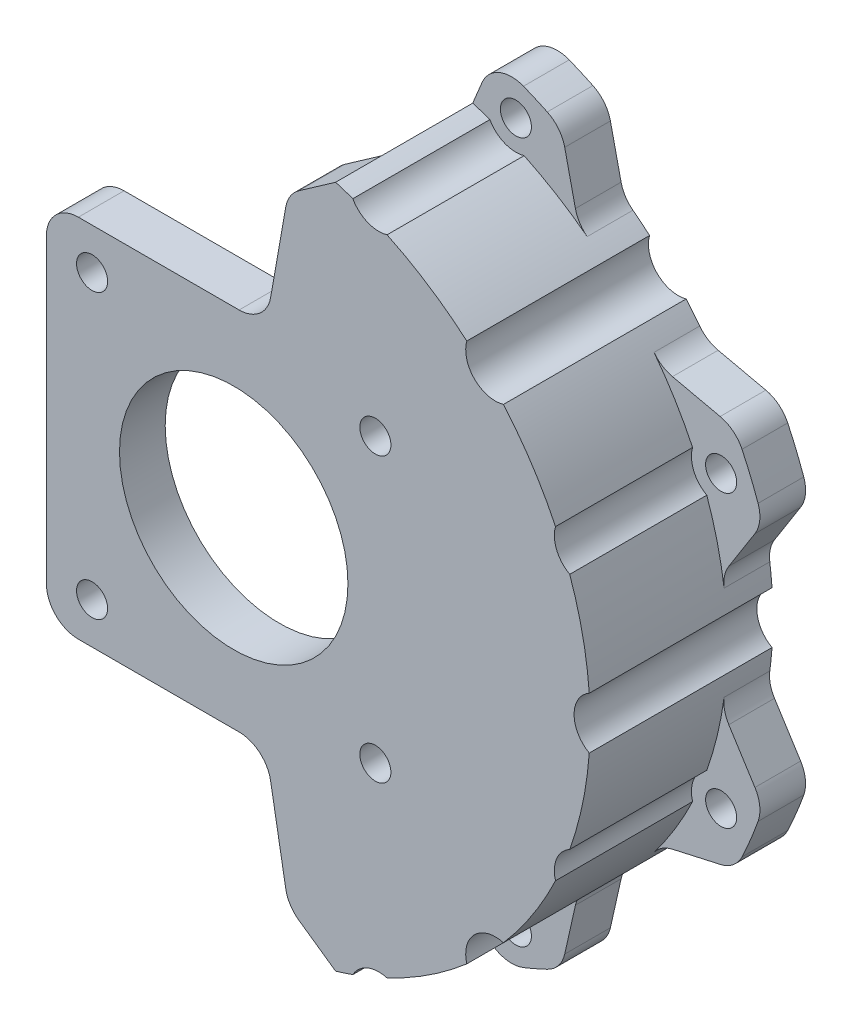
SolidWorks part; units mm, degrees
ref_plane "Alzado" through (0, 0, 0) normal (0, 0, 1) x (1, 0, 0)
ref_plane "Planta" through (0, 0, 0) normal (0, 1, 0) x (1, 0, 0)
ref_plane "Vista lateral" through (0, 0, 0) normal (1, 0, 0) x (0, 0, -1)
sketch "Croquis1" plane through (0, 0, 0) normal (0, 0, 1) x (1, 0, 0)
  line L0 (0, 0) -> (40.5, 0) construction
  line L1 (0, 0) -> (15.8814, 38.341) construction
  line L2 (13.4513, 42.9268) -> (10.7725, 36.4596)
  line L3 (0, 0) -> (38.341, 15.8814) construction
  line L4 (0, 0) -> (38.341, -15.8814) construction
  line L5 (0, 0) -> (15.8814, -38.341) construction
  line L7 (20.8423, 39.8653) -> (18.1635, 33.3982)
  line L8 (10.7725, 36.4596) -> (8.6471, 31.3285)
  line L9 (42.9268, 13.4513) -> (36.4596, 10.7725)
  line L10 (39.8653, 20.8423) -> (33.3982, 18.1635)
  line L11 (8.6471, -31.3285) -> (13.4513, -42.9268)
  line L12 (39.8653, -20.8423) -> (33.3982, -18.1635)
  line L13 (42.9268, -13.4513) -> (36.4596, -10.7725)
  line L16 (20.8423, -39.8653) -> (18.1635, -33.3982)
  line L18 (33.3982, 18.1635) -> (28.2671, 16.0382) [skipped]
  line L19 (36.4596, -10.7725) -> (31.3285, -8.6471) [skipped]
  line L20 (18.1635, -33.3982) -> (16.0382, -28.2671) [skipped]
  line L21 (13.4513, -42.9268) -> (8.6471, -31.3285) [skipped]
  circle A0 centre (0, 0) radius 40.5 construction
  circle A1 centre (15.8814, 38.341) radius 1.7
  circle A2 centre (0, 0) radius 41.5 construction
  circle A3 centre (0, 0) radius 41.5 construction
  circle A4 centre (38.341, 15.8814) radius 1.7
  circle A5 centre (0, 0) radius 41.5 construction
  circle A6 centre (38.341, -15.8814) radius 1.7
  circle A7 centre (0, 0) radius 41.5 construction
  circle A8 centre (15.8814, -38.341) radius 1.7
  arc A10 (13.4513, -42.9268) -> (20.8423, -39.8653) centre (0, 0) ccw
  arc A11 (8.6471, -31.3285) -> (8.6471, 31.3285) centre (0, 0) ccw
  arc A12 (33.3982, 18.1635) -> (18.1635, 33.3982) centre (0, 0) ccw
  arc A13 (36.4596, -10.7725) -> (36.4596, 10.7725) centre (0, 0) ccw
  arc A14 (18.1635, -33.3982) -> (33.3982, -18.1635) centre (0, 0) ccw
  arc A15 (39.8653, -20.8423) -> (42.9268, -13.4513) centre (0, 0) ccw
  arc A16 (42.9268, 13.4513) -> (39.8653, 20.8423) centre (0, 0) ccw
  arc A17 (20.8423, 39.8653) -> (13.4513, 42.9268) centre (0, 0) ccw
  point P9 (12.1119, 39.6932)
  point P22 (0, 0)
  point P45 (0, 0)
  dimension "D1" = 81
  dimension "D4" = 3.4
  dimension "D9" = 65
  dimension "D2" = 41.5
  dimension "D3" = 67.5
  dimension "D5" = 7
  dimension "D6" = 4
  dimension "D8" = 67.5
  dimension "D10" = 4
  dimension "D7" = 4
extrude "Saliente-Extruir1" add sketch "Croquis1" along normal blind 5
sketch "Croquis2" plane through (0, 0, 0) normal (0, 0, -1) x (-1, 0, 0)
  circle A0 centre (0, 0) radius 39.0124
extrude "Saliente-Extruir2" add sketch "Croquis2" against normal blind 20
sketch "Croquis3" plane through (0, 0, 20) normal (0, 0, 1) x (1, 0, 0)
  line L0 (0, 0) -> (-20.5, 0) construction
  line L1 (-15.5, -15.5) -> (15.5, -15.5) construction
  line L2 (-15.5, -15.5) -> (-15.5, 15.5) construction
  line L3 (-15.5, 15.5) -> (15.5, 15.5) construction
  line L4 (15.5, -15.5) -> (15.5, 15.5) construction
  line L5 (-15.5, -15.5) -> (15.5, 15.5) construction
  line L6 (-15.5, 15.5) -> (15.5, -15.5) construction
  line L7 (-20.5, 20) -> (-20.5, -20)
  line L8 (-20.5, 20) -> (3.5265, 20)
  line L9 (3.5265, 20) -> (6.7744, 38.4197)
  line L10 (3.5265, -20) -> (6.7744, -38.4197)
  line L11 (-20.5, -20) -> (3.5265, -20)
  circle A0 centre (-15.5, 15.5) radius 1.7
  circle A1 centre (15.5, 15.5) radius 1.7
  circle A2 centre (15.5, -15.5) radius 1.7
  circle A3 centre (-15.5, -15.5) radius 1.7
  circle A5 centre (0, 0) radius 39.0124 construction
  arc A6 (6.7744, 38.4197) -> (6.7744, -38.4197) centre (0, 0) ccw
  circle A7 centre (0, 0) radius 12.5
  point P0 (0, 0)
  point P16 (0, 0)
  point P18 (-20.5, 0)
  dimension "D3" = 3.4
  dimension "D6" = 25
  dimension "D2" = 31
  dimension "D4" = 40
  dimension "D5" = 20.5
  dimension "D7" = 100
  dimension "D1" = 4
extrude "Cortar-Extruir1" cut sketch "Croquis3" against normal blind 5
sketch "Croquis4" plane through (0, 0, 0) normal (0, 0, -1) x (-1, 0, 0)
  line L0 (-13.4513, 42.9268) -> (-11.1552, 37.3835)
  line L1 (-11.1552, 37.3835) -> (-9.8032, 34.1196)
  line L2 (0, 0) -> (35, 0) construction
  line L3 (-11.1552, -37.3835) -> (-9.8032, -34.1196)
  line L4 (-13.4513, -42.9268) -> (-11.1552, -37.3835)
  arc A0 (-9.8032, 34.1196) -> (-9.8032, -34.1196) centre (0, 0) ccw
  arc A1 (-13.4513, -42.9268) -> (-13.4513, 42.9268) centre (0, 0) ccw
  dimension "D1" = 71
  dimension "D2" = 44.985
extrude "Cortar-Extruir2" cut sketch "Croquis4" against normal blind 15
chamfer "Chaflán1" distance 4.75 angle 45 2 edges at (6.7744, 38.4197, 17.5) (6.7744, -38.4197, 17.5)
fillet "Redondeo2" radius 3.5 6 edges at (3.5265, 20, 17.5) (3.5265, -20, 17.5) (-20.5, -20, 17.5) (-20.5, 20, 17.5) (5.9496, -33.7419, 17.5) (5.9496, 33.7419, 17.5)
sketch "Croquis5" plane through (0, 0, 5) normal (0, 0, 1) x (1, 0, 0)
  circle A0 centre (15.8814, -38.341) radius 3.25
  dimension "D1" = 6.5
extrude "Cortar-Extruir3" cut sketch "Croquis5" along normal up to surface (15 mm away) up to face at (-13.8, -15.5, 20)
pattern_circular "MatrizC1" count 4 over 135 about axis through (0, 0, 20) along (0, 0, -1) of "Cortar-Extruir3" reverse direction yes
sketch "Croquis6" plane through (0, 0, 15) normal (0, 0, -1) x (-1, 0, 0)
  circle A0 centre (15.5, 15.5) radius 3.25
  circle A1 centre (15.5, -15.5) radius 3.25
  circle A2 centre (-15.5, -15.5) radius 3.25
  circle A3 centre (-15.5, 15.5) radius 3.25
  point P12 (0, 0)
  dimension "D1" = 6.5
  dimension "D2" = 4
extrude "Cortar-Extruir4" cut sketch "Croquis6" against normal blind 2.5
chamfer "Chaflán4" distance 2 angle 45 1 edges at (35.5, 0, 15)
sketch "Croquis8" plane through (0, 0, 0) normal (0, 0, -1) x (-1, 0, 0)
  line L0 (0, 0) -> (-50.5888, 0) construction
  line L5 (0, 0) -> (-38.341, -15.8814) construction
  circle A0 centre (-40.5, 0) radius 1.7 construction
  circle A1 centre (0, 0) radius 40.5 construction
  circle A2 centre (-28.6378, 28.6378) radius 1.7 construction
  circle A3 centre (0, 40.5) radius 1.7 construction
  circle A4 centre (28.6378, 28.6378) radius 1.7 construction
  circle A5 centre (40.5, 0) radius 1.7 construction
  circle A17 centre (-40.5, 0) radius 3.25
  circle A20 centre (-28.6378, -28.6378) radius 3.25
  circle A21 centre (-28.6378, 28.6378) radius 3.25
  point P17 (0, 0)
  dimension "D1" = 81
  dimension "D2" = 3.4
  dimension "D4" = 6.5
  dimension "D3" = 5
extrude "Cortar-Extruir5" cut sketch "Croquis8" against normal blind 32.5
chamfer "Chaflán5" distance 5.7 angle 45 6 edges at (34.3221, 18.5462, 2.5) (37.3835, 11.1552, 2.5) (37.3835, -11.1552, 2.5) (34.3221, -18.5462, 2.5) (18.5462, 34.3221, 2.5) (18.5462, -34.3221, 2.5) first distance on face at (33.1013, 20.3337, 8.3333) first distance on face at (37.7843, 9.0281, 8.3333) first distance on face at (37.7843, -9.0281, 8.3333) first distance on face at (33.1013, -20.3337, 8.3333) first distance on face at (20.3337, 33.1013, 8.3333) first distance on face at (20.3337, -33.1013, 8.3333)
fillet "Redondeo3" radius 3.5 14 edges at (31.7424, 22.68, 2.5) (39.8556, 20.8609, 2.5) (42.9331, 13.4313, 2.5) (38.4825, 6.4081, 2.5) (31.7424, -22.68, 2.5) (38.4825, -6.4081, 2.5) (42.9331, -13.4313, 2.5) (39.8556, -20.8609, 2.5) (13.4513, 42.9268, 2.5) (13.4513, -42.9268, 2.5) (20.8609, 39.8556, 2.5) (22.68, 31.7424, 2.5) (22.68, -31.7424, 2.5) (20.8609, -39.8556, 2.5)
